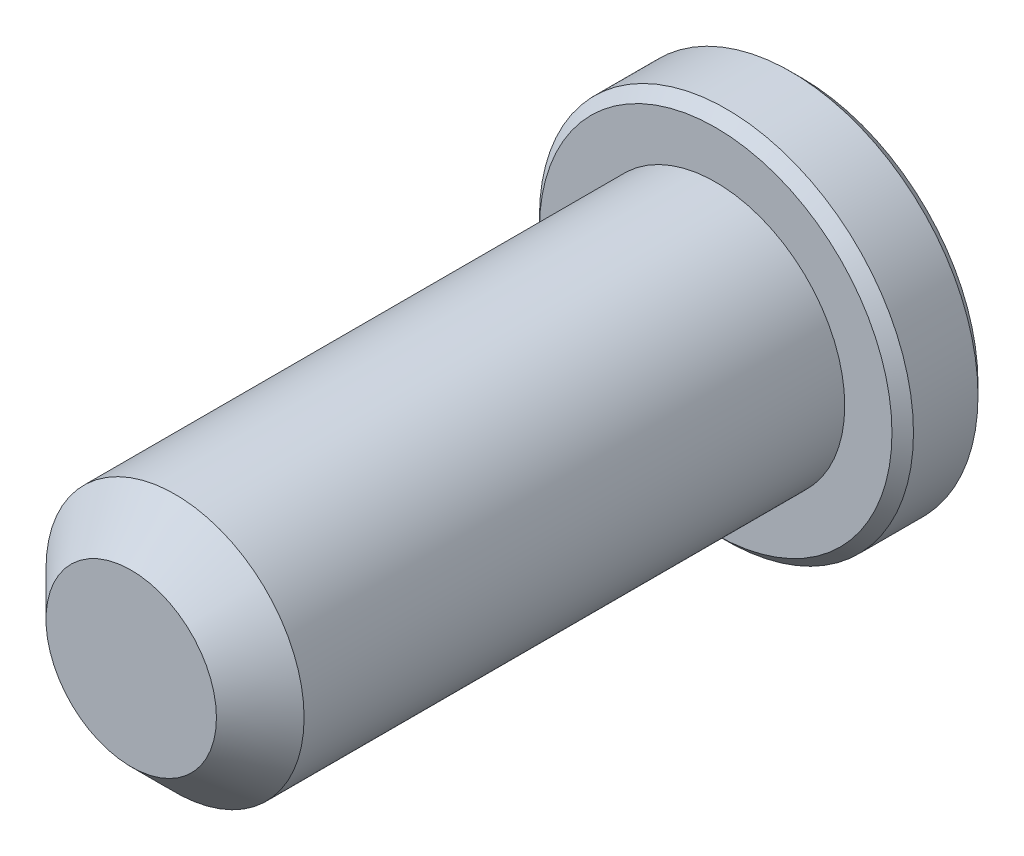
SolidWorks part; units mm, degrees
other "DetailItem1"
ref_plane "Front Plane" through (0, 0, 0) normal (0, 0, 1) x (1, 0, 0)
ref_plane "Top Plane" through (0, 0, 0) normal (0, 1, 0) x (1, 0, 0)
ref_plane "Right Plane" through (0, 0, 0) normal (1, 0, 0) x (0, 0, -1)
sketch "Sketch0" plane through (0, 0, 0) normal (1, 0, 0) x (0, 0, -1)
  line L0 (4.553, 0) -> (-4.553, 0) construction
  line L1 (4.5529, 2.54) -> (4.553, -2.54) construction
  line L2 (4.5529, 2.54) -> (3.3845, 2.54) construction
  line L3 (-4.553, 0) -> (-4.553, 1.7526) construction
  line L4 (-4.553, 1.7526) -> (-3.7592, 1.7526) construction
  point P3 (4.553, 0.7937)
  point P6 (4.553, 0)
  dimension "Head Diameter" = 5.08
  dimension "Drive Size" = 1.5875
  dimension "Head Height" = 1.1684
  dimension "Pitch" = 0.7937
  dimension "Thread Size Decimal Equivalent" = 3.5052
  dimension "Length" = 7.9375
sketch "Sketch1" plane through (0, 0, 0) normal (0, 0, 1) x (1, 0, 0)
  circle A0 centre (0, 0) radius 1.7526
extrude "Extrude1" add sketch "Sketch1" along normal up to vertex (4.553 mm away) from vertex up to point (0, 0, 4.553) starting at point (0, 2.54, -3.3845)
sketch "Sketch6" plane through (0, 0, 0) normal (0, 0, 1) x (1, 0, 0)
  circle A0 centre (0, 0) radius 2.54
extrude "Extrude2" add sketch "Sketch6" along normal up to vertex (-3.3845 mm away) from vertex up to point (0, 2.54, -3.3845) starting at point (0, 2.54, -4.5529)
sketch "Sketch7" plane through (0, 0, -4.5529) normal (0, 0, 1) x (1, 0, 0)
  line L1 (0, 0.9165) -> (-0.7937, 0.4583)
  line L2 (-0.7937, 0.4583) -> (-0.7937, -0.4583)
  line L3 (-0.7937, -0.4583) -> (0, -0.9165)
  line L4 (0, -0.9165) -> (0.7937, -0.4583)
  line L5 (0.7937, -0.4583) -> (0.7937, 0.4583)
  line L6 (0.7937, 0.4583) -> (0, 0.9165)
  circle A0 centre (0, 0) radius 0.7937 construction
extrude "Cut-Extrude1" cut sketch "Sketch7" along normal blind 0.8763
sketch "Sketch8" plane through (0, 0, -4.5529) normal (0, 0, 1) x (1, 0, 0)
  circle A0 centre (0, 0) radius 0.9165
extrude "Cut-Extrude2" cut sketch "Sketch8" along normal up to next (0.8763 mm away) draft 45
chamfer "Chamfer1" distance 0.1461 angle 45 2 edges at (2.54, 0, -3.3845) (2.54, 0, -4.5529)
chamfer "Chamfer2" distance 0.5953 angle 45 1 edges at (1.7526, 0, 4.553)
split "Split1" [suppressed] bodies to split 107
sketch "Sketch2" [suppressed] plane through (0, 0, 4.553) normal (0, 0, -1) x (-1, 0, 0)
  circle A1 centre (0, 0) radius 1.7526
curve "Helix/Spiral1" [suppressed] pitch 0.7937 height 8.7312 turns 11 parameters "pitch"=0.7937
sketch "Sketch3" [suppressed] plane through (0, 0, 0) normal (1, 0, 0) x (0, 0, -1)
  line L0 (-5.2971, 1.8385) -> (-4.9002, 1.1511) construction
  line L1 (-4.9002, 1.1511) -> (-4.5033, 1.8385) construction
  line L2 (-4.5033, 1.8385) -> (-5.2971, 1.8385) construction
  line L3 (-5.2475, 1.7526) -> (-4.553, 1.7526) construction
  line L4 (-4.9002, 1.8385) -> (-4.9002, 1.7526) construction
  line L5 (-4.9002, 1.7526) -> (-4.9002, 1.237) construction
  line L6 (-4.9002, 1.237) -> (-4.9002, 1.1511) construction
  line L7 (-4.9498, 1.237) -> (-4.8506, 1.237)
  line L8 (-5.2723, 1.7956) -> (-4.5281, 1.7956)
  line L9 (-4.8506, 1.237) -> (-4.5281, 1.7956)
  line L10 (-4.9498, 1.237) -> (-5.2723, 1.7956)
  line L11 (-3.9576, -1.7526) -> (3.3845, -1.7526) construction
  point P14 (-4.9002, 1.7956)
  point P17 (-2.5686, -1.7526)
  dimension "D1" = 0.7937
  dimension "D2" = 0.0992
  dimension "D3" = 1.9844
sweep "Cut-Sweep1" [suppressed] cut profiles "Sketch3" path "Helix/Spiral1"
sketch "Sketch9" [suppressed] plane through (0, 0, 0) normal (1, 0, 0) x (0, 0, -1)
  line L0 (3.3845, 1.7526) -> (2.1907, 1.7526)
  line L1 (2.1907, 1.7526) -> (2.1907, 0) construction
  line L2 (4.553, 0) -> (-4.553, 0) construction
  line L3 (2.1907, 0) -> (3.3845, 0)
  line L4 (3.3845, 0) -> (3.3845, 1.7526)
  line L5 (2.1907, 1.7526) -> (1.5893, 1.1511)
  line L7 (1.5893, 1.1511) -> (1.5893, 0)
  line L8 (1.5893, 0) -> (2.1907, 0)
  dimension "D1" = 45
  dimension "Relief" = 1.1938
revolve "Revolve1" [suppressed] add sketch "Sketch9" angle 360 about L3
ref_axis "Axis1" through (0, 0, 5.0128) along (0, 0, -1)
equation "\"D3@Helix/Spiral1\"=\"Length@Sketch0\"+\"Pitch@Sketch0\""
equation "\"D1@Cut-Extrude1\"=\"Head Height@Sketch0\"*.75"
equation "\"D1@Chamfer1\"=\"Head Height@Sketch0\" * .125"
equation "\"pitch@Helix/Spiral1\"=\"Pitch@Sketch0\""
equation "\"D2@Sketch3\"=\"D1@Sketch3\"/8"
equation "\"D1@Sketch3\" = \"Pitch@Sketch0\""
equation "\"D3@Sketch3\" = \"Pitch@Sketch0\" * 2.5"
equation "\"D1@Chamfer2\" = \"Pitch@Sketch0\" * 0.75"
